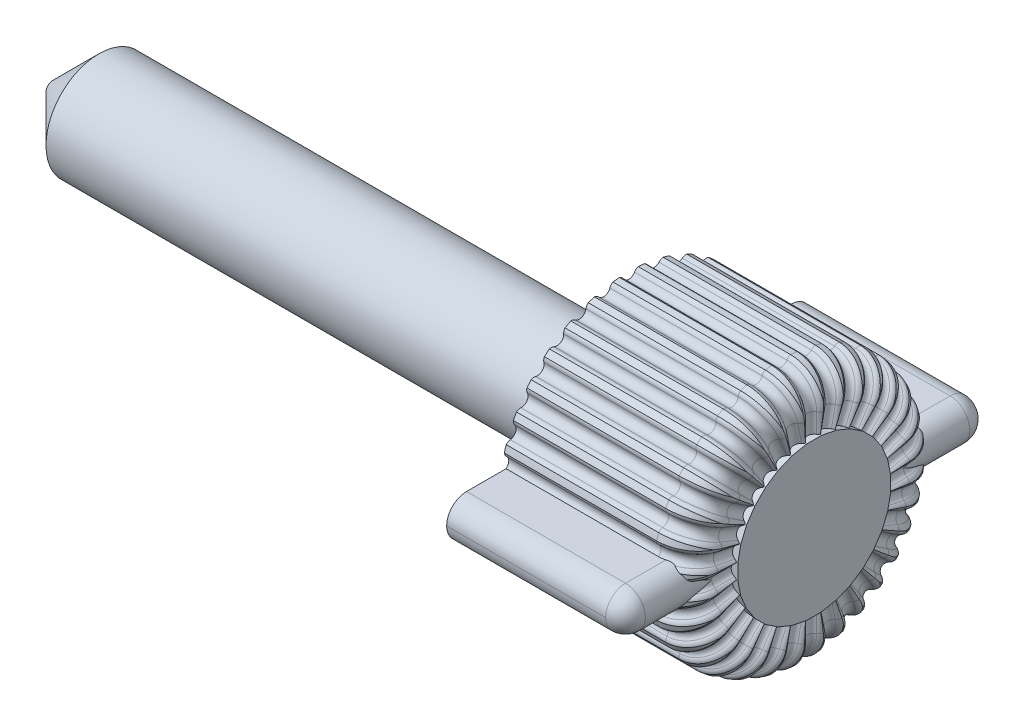
SolidWorks part; units mm, degrees
ref_plane "Plane1" through (0, 0, 0) normal (0, 0, 1) x (1, 0, 0)
ref_plane "Plane2" through (0, 0, 0) normal (0, 1, 0) x (1, 0, 0)
ref_plane "Plane3" through (0, 0, 0) normal (1, 0, 0) x (0, 0, -1)
sketch "Sketch1" plane through (0, 0, 0) normal (0, 0, 1) x (1, 0, 0)
  line L0 (0, 0) -> (29.21, 0) construction
  line L1 (0, 0) -> (0, 2.032)
  line L2 (0, 2.032) -> (23.622, 2.032)
  line L3 (23.622, 2.032) -> (23.622, 3.175)
  line L4 (23.622, 3.175) -> (22.098, 3.175)
  line L5 (22.098, 3.175) -> (22.098, 4.953)
  line L6 (22.098, 4.953) -> (27.94, 4.953)
  line L7 (29.21, 3.683) -> (29.21, 0)
  line L8 (29.21, 0) -> (0, 0)
  arc A0 (29.21, 3.683) -> (27.94, 4.953) centre (27.94, 3.683) ccw
  dimension "D2" = 1.27
  dimension "D1" = 3.175
  dimension "D3" = 7.112
  dimension "D4" = 1.524
  dimension "D5" = 29.21
  dimension "D6" = 2.032
  dimension "D7" = 4.953
revolve "Base-Revolve" add sketch "Sketch1" angle 360 about L0
sketch "Sketch3" plane through (0, 0, 0) normal (0, 0, 1) x (1, 0, 0)
  line L1 (28.956, 3.683) -> (28.956, 2.9301)
  line L2 (28.956, 3.683) -> (28.956, -3.683)
  line L3 (27.94, 4.699) -> (22.098, 4.699)
  line L4 (27.94, 4.953) -> (22.098, 4.953) construction
  line L5 (27.94, 4.699) -> (22.098, 4.699)
  arc A1 (28.956, 3.683) -> (27.94, 4.699) centre (27.94, 3.683) ccw
  arc A2 (28.956, 3.683) -> (27.94, 4.699) centre (27.94, 3.683) ccw
  dimension "D2" = 2.0229
  dimension "D1" = 0.254
ref_plane "Plane4" through (28.956, 2.9301, 0) normal (0, -1, 0) x (1, 0, 0)
sketch "Sketch4" plane through (28.956, 2.9301, 0) normal (0, -1, 0) x (1, 0, 0)
  line L0 (-28.956, 0) -> (0.254, 0) construction
  line L4 (0.254, -3.683) -> (0.254, 3.683) construction
  line L6 (0.254, 0.4399) -> (0.254, -0.4399)
  arc A0 (0.127, 0.22) -> (0.127, -0.22) centre (0.254, 0) ccw
  arc A1 (0.254, 0.4399) -> (0.127, 0.22) centre (0, 0.4399) cw
  arc A2 (0.254, -0.4399) -> (0.127, -0.22) centre (0, -0.4399) ccw
  dimension "D1" = 0.254
  dimension "D2" = 0.254
sweep "Cut-Sweep1" cut profiles "Sketch4" path "Sketch3"
pattern_circular "CirPattern1" count 32 every 11.25 about axis through (0, 0, 0) along (1, 0, 0) of "Cut-Sweep1"
chamfer "Chamfer1" distance 1.778 angle 45 1 edges at (0, 0, 2.032)
sketch "Sketch6" plane through (0, 0, 0) normal (0, 0, 1) x (1, 0, 0)
  line L0 (22.098, 0.762) -> (28.194, 0.762)
  line L1 (22.098, 4.9399) -> (22.098, 4.9152) construction
  line L2 (29.21, -3.683) -> (29.21, 3.6566) construction
  line L3 (28.194, -0.762) -> (22.098, -0.762)
  line L4 (22.098, 0.762) -> (22.098, -0.762)
  arc A0 (28.194, 0.762) -> (28.194, -0.762) centre (28.194, 0) cw
  dimension "D1" = 0.254
  dimension "D2" = 1.524
extrude "Boss-Extrude1" add sketch "Sketch6" along normal mid plane 13.97
fillet "Fillet4" radius 0.762 6 edges at (25.146, -0.762, -6.985) (28.956, 0, -6.985) (25.146, 0.762, -6.985) (25.146, -0.762, 6.985) (28.956, 0, 6.985) (25.146, 0.762, 6.985)
sketch "Sketch7" plane through (23.622, 0, 0) normal (-1, 0, 0) x (0, 0, 1)
  circle A1 centre (0, 0) radius 2.032
  circle A2 centre (0, 0) radius 3.175
  arc A3 (1.8837, 0.762) -> (-1.8837, 0.762) centre (0, 0) ccw construction
  arc A4 (3.0822, 0.762) -> (-3.0822, 0.762) centre (0, 0) ccw construction
extrude "Cut-Extrude1" cut sketch "Sketch7" along normal up to surface (1.524 mm away) up to face at (22.098, 0, 0)
